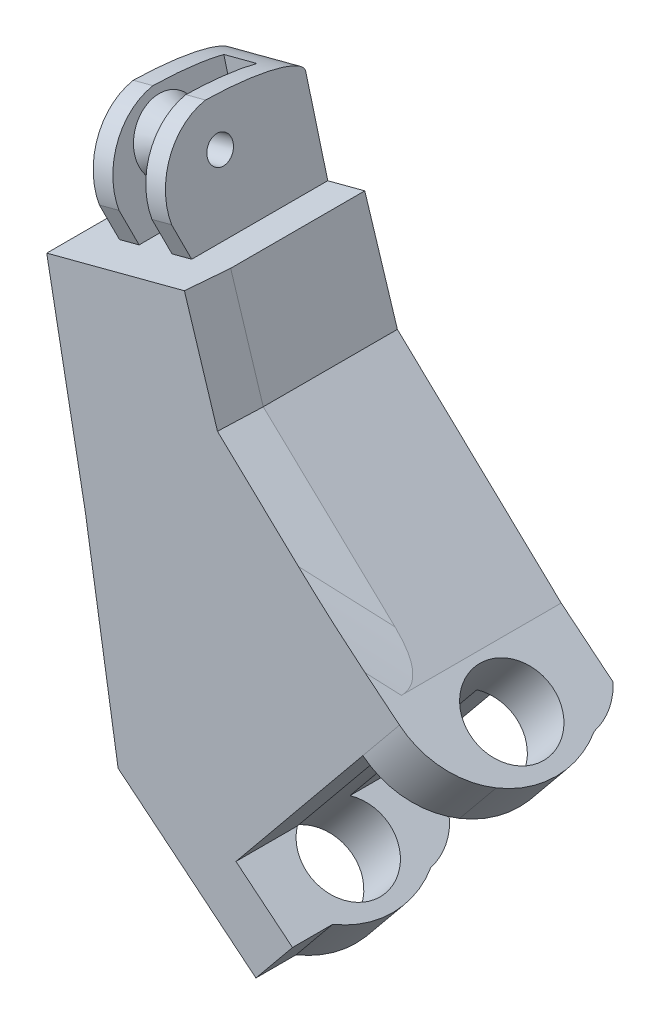
SolidWorks part; units mm, degrees
ref_plane "Plan de face" through (0, 0, 0) normal (0, 0, 1) x (1, 0, 0)
ref_plane "Plan de dessus" through (0, 0, 0) normal (0, 1, 0) x (1, 0, 0)
ref_plane "Plan de droite" through (0, 0, 0) normal (1, 0, 0) x (0, 0, -1)
sketch "Sketch1" plane through (0, 0, 0) normal (0, 0, 1) x (1, 0, 0)
  line L0 (0, 0) -> (-3.1591, 10.05)
  line L1 (-3.1591, 10.05) -> (-6.7469, 9.1054)
  line L2 (-6.7469, 9.1054) -> (-9.3954, 19.1654)
  line L3 (-9.3954, 19.1654) -> (-16.3968, 17.3221)
  line L4 (-16.3968, 17.3221) -> (-13.7483, 7.2621)
  line L5 (-13.7483, 7.2621) -> (-16.9879, 6.4092)
  line L6 (-16.9879, 6.4092) -> (-13.2498, -13.4308)
  line L7 (0, 0) -> (-22.3263, 0) construction
  line L8 (-13.2498, -13.4308) -> (-10.0692, -33.3773)
  line L9 (-10.0692, -33.3773) -> (4.6643, -45.4322)
  line L10 (4.6643, -45.4322) -> (8.2105, -41.0981)
  line L11 (8.2105, -41.0981) -> (1.3533, -35.4876)
  line L12 (1.3533, -35.4876) -> (13.6573, -20.4497)
  line L13 (13.6573, -20.4497) -> (20.5145, -26.0603)
  line L14 (20.5145, -26.0603) -> (24.0607, -21.7261)
  line L15 (24.0607, -21.7261) -> (15.88, -15.0327)
  line L16 (15.88, -15.0327) -> (0, 0)
  dimension "D1" = 72.55
  dimension "D2" = 7.24
  dimension "D3" = 10.06
  dimension "D4" = 10.06
  dimension "D5" = 10.05
  dimension "D6" = 94.08
  dimension "D7" = 92.7
  dimension "D8" = 19.84
  dimension "D9" = 19.43
  dimension "D10" = 181.61
  dimension "D11" = 138.35
  dimension "D12" = 5.6
  dimension "D13" = 8.86
  dimension "D14" = 90
  dimension "D15" = 15.88
  dimension "D16" = 8.86
  dimension "D17" = 5.6
  dimension "D18" = 10.57
  dimension "D19" = 175.86
  dimension "D20" = 3.35
  dimension "D21" = 3.71
  dimension "D22" = 30.63
  dimension "D23" = 72.55
extrude "Boss-Extrude1" add sketch "Sketch1" along normal blind 17
sketch "Sketch2" plane through (-11.0691, -2.9142, 0) normal (-0.967, -0.2546, 0) x (0, 0, 1)
  line L0 (14.331, 13.6941) -> (13.19, 10.5231)
  line L1 (17, 10.5231) -> (0, 10.5231) construction
  line L2 (13.19, 10.5231) -> (20.4157, 10.5231)
  line L3 (20.4157, 10.5231) -> (20.4157, 21.9288)
  line L4 (20.4157, 21.9288) -> (-2.093, 21.9288)
  line L5 (-2.093, 21.9288) -> (-2.093, 20.9811)
  line L6 (-2.093, 20.9811) -> (9.1614, 20.9259)
  line L7 (17, 20.9259) -> (0, 20.9259) construction
  line L8 (17, 20.9259) -> (17, 10.5231) construction
  arc A0 (14.331, 13.6941) -> (9.1614, 20.9259) centre (8.3001, 14.8466) ccw
  dimension "D4" = 6.14
  dimension "D1" = 3.81
  dimension "D2" = 70.21
  dimension "D3" = 3.37
extrude "Cut-Extrude1" cut sketch "Sketch2" against normal blind 17
sketch "Sketch3" plane through (-11.0691, -2.9142, 0) normal (-0.967, -0.2546, 0) x (0, 0, 1)
  line L0 (0, 20.9259) -> (0, 10.5231) construction
  line L1 (9.1614, 20.9259) -> (0, 20.9259) construction
  circle A0 centre (8.8, 16.9259) radius 1.25
  dimension "D3" = 2.5
  dimension "D1" = 8.8
  dimension "D2" = 4
extrude "Cut-Extrude2" cut sketch "Sketch3" against normal blind 17
sketch "Sketch4" plane through (-5.3278, 20.2363, 0) normal (-0.2546, 0.967, 0) x (0.967, 0.2546, 0)
  line L0 (-7.8263, 0) -> (-7.8263, -1.667) construction
  line L1 (-9.4763, -2.5) -> (-6.1763, -2.5)
  line L2 (-9.4763, -2.5) -> (-9.4763, -14.9997)
  line L3 (-9.4763, -14.9997) -> (-6.1763, -14.9997)
  line L4 (-6.1763, -2.5) -> (-6.1763, -14.9997)
  line L5 (-4.2063, 0) -> (-11.4463, 0) construction
  dimension "D1" = 3.3
  dimension "D2" = 1.65
  dimension "D3" = 2.5
extrude "Cut-Extrude3" cut sketch "Sketch4" against normal up to surface (10.4028 mm away)
ref_plane "Plane1" through (-7.5684, -1.9926, 0) normal (-0.967, -0.2546, 0) x (0, 0, 1)
sketch "Sketch5" plane through (-7.5684, -1.9926, 0) normal (-0.967, -0.2546, 0) x (0, 0, 1)
  circle A0 centre (8.8, 16.9259) radius 1.25
extrude "Extrude-Thin1" add sketch "Sketch5" along normal up to surface (1.65 mm away) draft 30 and the other way up to surface (1.65 mm away) draft 30 thin
sketch "Sketch6" plane through (-11.0691, -2.9142, 0) normal (-0.967, -0.2546, 0) x (0, 0, 1)
  circle A0 centre (8.8, 16.9259) radius 1.25
extrude "Cut-Extrude4" cut sketch "Sketch6" against normal through all
sketch "Sketch7" plane through (-20.396, -24.9279, 0) normal (-0.6332, -0.774, 0) x (-0.774, 0.6332, 0)
  line L0 (-28.3297, 0) -> (-23.5997, 0)
  line L1 (-13.343, 0) -> (-32.3797, 0) construction
  line L2 (-23.5997, 0) -> (-23.5997, -17)
  line L3 (-13.343, -17) -> (-32.3797, -17) construction
  line L4 (-23.5997, -17) -> (-30.5997, -17)
  line L5 (-30.5997, -17) -> (-30.5997, -13.1)
  line L6 (-32.3797, -17) -> (-32.3797, 0) construction
  arc A0 (-30.5997, -13.1) -> (-30.5997, -3.6) centre (-23.0733, -8.35) cw
  spline S0 degree 2 poles (-28.3297, 0) (-30.1662, -1.3676) (-30.5997, -3.6) knots 0 0 0 1 1 1
  line M7 (-13.343, 0) -> (-32.3797, 0)
  line M8 (-32.3797, 0) -> (-32.3797, -17)
  line M9 (-32.3797, -17) -> (-13.343, -17)
  dimension "D6" = 8.9
  dimension "D7" = 4.36
  dimension "D1" = 4.73
  dimension "D2" = 7
  dimension "D3" = 3.9
  dimension "D4" = 1.78
  dimension "D5" = 9.5
  dimension "D8" = 3.6
extrude "Cut-Extrude5" cut sketch "Sketch7" against normal blind 47 contours S0 L5 A0 M7 M8 M9
sketch "Sketch8" plane through (-4.5458, -5.5559, 0) normal (-0.6332, -0.774, 0) x (0.774, -0.6332, 0)
  line L0 (30.5997, 13.1) -> (30.5997, 17)
  line L1 (30.5997, 17) -> (23.5197, 17)
  arc A0 (23.5197, 17) -> (30.5997, 13.1) centre (23.5197, 8.6235) cw
extrude "Cut-Extrude6" cut sketch "Sketch8" against normal blind 51
sketch "Sketch9" plane through (-20.396, -24.9279, 0) normal (-0.6332, -0.774, 0) x (-0.774, 0.6332, 0)
  line L0 (-13.343, -17) -> (-30.5997, -17) construction
  line L1 (-30.5997, -17) -> (-30.5997, -13.1) construction
  circle A0 centre (-26.5997, -8.5) radius 4
  dimension "D3" = 8
  dimension "D1" = 8.5
  dimension "D2" = 4
extrude "Cut-Extrude7" cut sketch "Sketch9" against normal blind 51
chamfer "Chamfer2" distance 4 distance2 0.5 2 edges at (-1.5796, 5.025, 17) (7.94, -7.5164, 17)
fillet "Fillet3" radius 30 1 edges at (13.1999, -12.8399, 15)
fillet "Fillet4" radius 2 1 edges at (-12.8961, 18.2438, 0)
